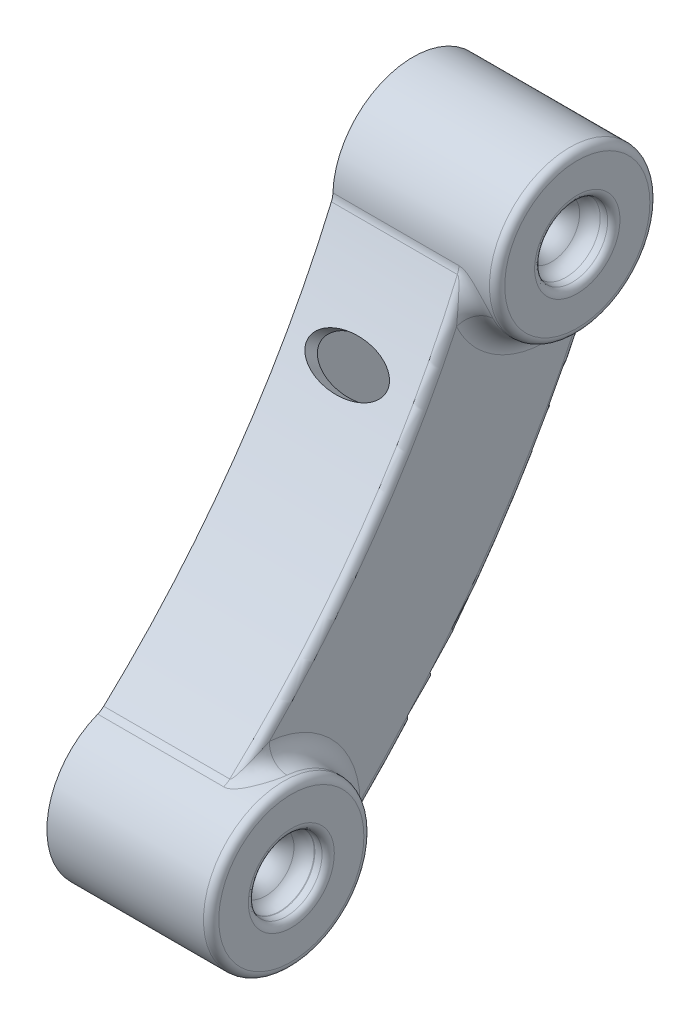
SolidWorks part; units mm, degrees
material "ABS"
ref_plane "Front Plane" through (0, 0, 0) normal (0, 0, 1) x (1, 0, 0)
ref_plane "Top Plane" through (0, 0, 0) normal (0, 1, 0) x (1, 0, 0)
ref_plane "Right Plane" through (0, 0, 0) normal (1, 0, 0) x (0, 0, -1)
sketch "Sketch1" plane through (0, 0, 0) normal (1, 0, 0) x (0, 0, -1)
  arc A0 (41.5746, 47.3049) -> (-33.3061, -58.963) centre (-210.024, 145.0757) cw construction
  arc A1 (-20.6251, -73.6045) -> (59.629, 40.289) centre (-210.024, 145.0757) ccw
  arc A2 (-45.9871, -44.3215) -> (23.5203, 54.3208) centre (-210.024, 145.0757) ccw
  arc A3 (-45.9871, -44.3215) -> (-20.6251, -73.6045) centre (-33.3061, -58.963) ccw
  arc A4 (59.629, 40.289) -> (23.5203, 54.3208) centre (41.5746, 47.3049) ccw
  point P3 (10.6273, -10.4043)
  dimension "D1" = 130
extrude "Boss-Extrude1" add sketch "Sketch1" along normal blind 40
fillet "Fillet1" radius 2 4 edges at (40, 0.7527, 5.2063) (40, 65.3593, -48.5905) (40, -21.5613, -26.4609) (40, -71.644, 47.9476)
fillet "Fillet2" radius 2 4 edges at (0, -21.5613, -26.4609) (0, 65.3593, -48.5905) (0, 0.7527, 5.2063) (0, -71.644, 47.9476)
sketch "Sketch3" plane through (40, 0, 0) normal (1, 0, 0) x (0, 0, -1)
  circle A0 centre (41.5746, 47.3049) radius 21
  circle A1 centre (-33.3061, -58.963) radius 21
  dimension "D1" = 42
  dimension "D2" = 42
extrude "Boss-Extrude2" add sketch "Sketch3" along normal blind 10 and the other way blind 40
fillet "Fillet3" radius 2 4 edges at (0, -73.0553, 48.8755) (0, 66.7079, -49.6074) (50, 47.3049, -62.5746) (50, -58.963, 12.3061)
sketch "Sketch4" plane through (50, 0, 0) normal (1, 0, 0) x (0, 0, -1)
  circle A0 centre (41.5746, 47.3049) radius 9
  circle A1 centre (-33.3061, -58.963) radius 9
  dimension "D1" = 18
  dimension "D2" = 18
extrude "Cut-Extrude1" cut sketch "Sketch4" against normal blind 10
draft "Draft1" type of draft neutral plane draft angle 1 faces to draft 1 face at (40, -58.963, 24.3061) neutral plane through (40, -58.963, 33.3061) neutral plane normal (1, 0, 0) parameters "D1"=1
fillet "Fillet5" radius 5 1 edges at (40, -58.963, 24.3061)
fillet "Fillet6" radius 5 1 edges at (50, -58.963, 24.1316)
fillet "Fillet7" radius 5 1 edges at (50, 47.3049, -50.5746)
fillet "Fillet8" radius 5 1 edges at (40, 47.3049, -50.5746)
sketch "Sketch5" plane through (0, 0, 0) normal (-1, 0, 0) x (0, 0, 1)
  arc A12 (-53.1045, 34.8124) -> (17.6628, -65.6179) centre (210.024, 145.0757) ccw
  arc A13 (17.6628, -65.6179) -> (38.1002, -42.653) centre (33.3061, -58.963) ccw
  arc A14 (-24.6025, 46.3323) -> (38.1002, -42.653) centre (210.024, 145.0757) ccw
  arc A15 (-24.6025, 46.3323) -> (-53.1045, 34.8124) centre (-41.5746, 47.3049) ccw
  arc A16 (-53.1045, 34.8124) -> (17.6628, -65.6179) centre (210.024, 145.0757) ccw
  arc A17 (17.6628, -65.6179) -> (38.1002, -42.653) centre (33.3061, -58.963) ccw
  arc A18 (-24.6025, 46.3323) -> (38.1002, -42.653) centre (210.024, 145.0757) ccw
  arc A19 (-24.6025, 46.3323) -> (-53.1045, 34.8124) centre (-41.5746, 47.3049) ccw
  point P3 (-10.8163, -10.5375)
  dimension "D1" = 2
extrude "Cut-Extrude2" cut sketch "Sketch5" against normal blind 35
sketch "Sketch6" plane through (0, 0, 0) normal (-1, 0, 0) x (0, 0, 1)
  arc A4 (-54.7852, 33.6491) -> (16.0019, -66.8092) centre (210.024, 145.0757) ccw
  arc A5 (16.0019, -66.8092) -> (39.1199, -40.8743) centre (33.3061, -58.963) ccw
  arc A6 (-22.5845, 46.6942) -> (39.1199, -40.8743) centre (210.024, 145.0757) ccw
  arc A7 (-22.5845, 46.6942) -> (-54.7852, 33.6491) centre (-41.5746, 47.3049) ccw
  arc A8 (-54.7852, 33.6491) -> (16.0019, -66.8092) centre (210.024, 145.0757) ccw
  arc A9 (16.0019, -66.8092) -> (39.1199, -40.8743) centre (33.3061, -58.963) ccw
  arc A10 (-22.5845, 46.6942) -> (39.1199, -40.8743) centre (210.024, 145.0757) ccw
  arc A11 (-22.5845, 46.6942) -> (-54.7852, 33.6491) centre (-41.5746, 47.3049) ccw
  dimension "D1" = 0
extrude "Boss-Extrude3" add sketch "Sketch6" against normal blind 7
sketch "Sketch7" plane through (0, 0, 0) normal (-1, 0, 0) x (0, 0, 1)
  circle A0 centre (-41.5746, 47.3049) radius 11
  circle A1 centre (33.3061, -58.963) radius 11
  dimension "D1" = 22
  dimension "D2" = 22
extrude "Cut-Extrude3" cut sketch "Sketch7" against normal blind 3
sketch "Sketch8" plane through (3, 0, 0) normal (-1, 0, 0) x (0, 0, 1)
  circle A0 centre (-41.5746, 47.3049) radius 1.5
  circle A1 centre (33.3061, -58.963) radius 1.5
  dimension "D1" = 3
  dimension "D2" = 3
extrude "Cut-Extrude4" cut sketch "Sketch8" against normal blind 13
sketch "Sketch9" plane through (0, 0, 0) normal (-1, 0, 0) x (0, 0, 1)
  arc A0 (5.2471, -45.5881) -> (19.5425, -31.0693) centre (28.8142, -54.4955) cw construction
  arc A1 (17.9088, -26.9417) -> (1.0947, -44.0186) centre (28.8142, -54.4955) ccw
  arc A2 (21.1761, -35.1969) -> (9.3995, -47.1575) centre (28.8142, -54.4955) ccw
  arc A3 (21.1761, -35.1969) -> (17.9088, -26.9417) centre (19.5425, -31.0693) ccw
  arc A4 (1.0947, -44.0186) -> (9.3995, -47.1575) centre (5.2471, -45.5881) ccw
  point P3 (10.8616, -36.8191)
extrude "Cut-Extrude5" cut sketch "Sketch9" against normal blind 13
sketch "Sketch10" plane through (0, 0, 0) normal (-1, 0, 0) x (0, 0, 1)
  line L1 (30.1932, -32.2559) -> (33.1416, -35.1969)
  line L2 (33.1416, -35.1969) -> (8.8115, -59.9933)
  line L3 (8.8115, -59.9933) -> (5.9216, -57.1173)
  line L5 (3.6776, -49.7405) -> (1.1214, -52.1539)
  line L6 (1.1214, -52.1539) -> (5.9216, -57.1173)
  line L7 (21.1761, -35.1969) -> (28.4389, -30.4591)
  line L8 (28.4389, -30.4591) -> (30.1932, -32.2559)
  arc A0 (1.0947, -44.0186) -> (9.3995, -47.1575) centre (5.2471, -45.5881) ccw construction
  arc A3 (21.1761, -35.1969) -> (9.3995, -47.1575) centre (28.8142, -54.4955) ccw construction
  arc A4 (3.6776, -49.7405) -> (9.3995, -47.1575) centre (5.2471, -45.5881) ccw
  arc A7 (21.1761, -35.1969) -> (9.3995, -47.1575) centre (28.8142, -54.4955) ccw
  arc A8 (-22.5845, 46.6942) -> (39.1199, -40.8743) centre (210.024, 145.0757) ccw construction
  arc A9 (-54.7852, 33.6491) -> (16.0019, -66.8092) centre (210.024, 145.0757) ccw construction
extrude "Boss-Extrude4" add sketch "Sketch10" against normal blind 36
sketch "Sketch11" plane through (35, 0, 0) normal (-1, 0, 0) x (0, 0, 1)
  circle A0 centre (33.3061, -58.963) radius 1.5
  circle A1 centre (-41.5746, 47.3049) radius 1.5
extrude "Cut-Extrude6" cut sketch "Sketch11" against normal through all
fillet "Fillet9" radius 5 14 edges at (0.768, -67.7575, 14.7049) (20, -68.0143, 14.3569) (38.5897, -67.8015, 14.2567) (40, -44.8707, 17.7367) (0.7707, -39.4834, 39.9383) (20, -39.1127, 40.1593) (0.7707, 46.9969, -20.9993) (20, 47.0803, -20.5758) (0.768, 32.7467, -56.1146) (20, 32.5055, -56.4735) (39.177, 31.8304, -55.7711) (40, 27.902, -33.5419) (39.2032, -38.8228, 39.2535) (38.6276, 46.832, -20.58)
sketch "Sketch12" plane through (0, 0, 0) normal (-1, 0, 0) x (0, 0, 1)
  circle A0 centre (-41.5746, 47.3049) radius 11
  circle A1 centre (-41.5746, 47.3049) radius 1.5
  circle A2 centre (33.3061, -58.963) radius 11
  circle A3 centre (33.3061, -58.963) radius 1.5
extrude "Boss-Extrude5" add sketch "Sketch12" against normal blind 40
sketch "Sketch14" plane through (0, 0, 0) normal (-1, 0, 0) x (0, 0, 1)
  arc A12 (30.5959, -28.374) -> (32.3293, -30.1495) centre (210.0229, 145.0746) ccw
  arc A13 (-19.5747, 47.2814) -> (30.5959, -28.374) centre (210.024, 145.0757) ccw
  arc A14 (-19.5747, 47.2814) -> (-57.3202, 31.9401) centre (-41.5746, 47.3049) ccw
  arc A15 (-57.3202, 31.9401) -> (13.5396, -68.6214) centre (210.024, 145.0757) ccw
  arc A16 (13.5396, -68.6214) -> (40.6855, -38.2375) centre (33.3061, -58.963) ccw
  arc A17 (32.3293, -30.1495) -> (40.6855, -38.2375) centre (210.024, 145.0757) ccw
  arc A18 (30.5959, -28.374) -> (32.3293, -30.1495) centre (210.0229, 145.0746) ccw
  arc A19 (-19.5747, 47.2814) -> (30.5959, -28.374) centre (210.024, 145.0757) ccw
  arc A20 (-19.5747, 47.2814) -> (-57.3202, 31.9401) centre (-41.5746, 47.3049) ccw
  arc A21 (-57.3202, 31.9401) -> (13.5396, -68.6214) centre (210.024, 145.0757) ccw
  arc A22 (13.5396, -68.6214) -> (40.6855, -38.2375) centre (33.3061, -58.963) ccw
  arc A23 (32.3293, -30.1495) -> (40.6855, -38.2375) centre (210.024, 145.0757) ccw
  dimension "D1" = 3
extrude "Cut-Extrude7" cut sketch "Sketch14" against normal blind 5
ref_plane "Plane1" through (0, 8.2155, 11.6591) normal (0, 0.576, 0.8174) x (1, 0, 0)
sketch "Sketch15" plane through (0, 8.2155, 11.6591) normal (0, 0.576, 0.8174) x (1, 0, 0)
  ellipse E0 centre (20.7051, 23.5238) end of major axis (31.398, 23.5238) minor radius 5.9262
extrude "Cut-Extrude8" cut sketch "Sketch15" against normal blind 27
sketch "Sketch16" plane through (5, 0, 0) normal (-1, 0, 0) x (0, 0, 1)
  circle A0 centre (33.3061, -58.963) radius 11
  circle A1 centre (33.3061, -58.963) radius 1.5
  circle A2 centre (-41.5746, 47.3049) radius 1.5
  circle A3 centre (-41.5746, 47.3049) radius 11
  dimension "D1" = 22
  dimension "D2" = 22
extrude "Cut-Extrude9" cut sketch "Sketch16" against normal blind 3
sketch "Sketch17" plane through (5, 0, 0) normal (-1, 0, 0) x (0, 0, 1)
  circle A0 centre (-41.5746, 47.3049) radius 11
  circle A1 centre (-41.5746, 47.3049) radius 19
  circle A2 centre (33.3061, -58.963) radius 11
  circle A3 centre (33.3061, -58.963) radius 19
  dimension "D1" = 38
  dimension "D2" = 38
extrude "Boss-Extrude6" add sketch "Sketch17" against normal blind 33
sketch "Sketch19" plane through (5, 0, 0) normal (-1, 0, 0) x (0, 0, 1)
  point P0 (33.3061, -58.963)
  point P1 (-41.5746, 47.3049)
sketch "Sketch20" plane through (40, 0, 0) normal (1, 0, 0) x (0, 0, -1)
  circle A0 centre (41.5746, 47.3049) radius 4
  circle A1 centre (-33.3061, -58.963) radius 4.0865
extrude "Cut-Extrude10" cut sketch "Sketch20" against normal blind 20
fillet "Fillet10" radius 10 1 edges at (40, 47.3049, -45.5746)
fillet "Fillet11" radius 10 1 edges at (40, -58.963, 29.2196)
sketch "Sketch21" plane through (50, 0, 0) normal (1, 0, 0) x (0, 0, -1)
  circle A0 centre (41.5746, 47.3049) radius 21
  circle A1 centre (-33.3061, -58.963) radius 21
extrude "Cut-Extrude11" cut sketch "Sketch21" against normal blind 2
fillet "Fillet12" radius 2 2 edges at (48, -58.963, 12.3061) (48, -58.963, 43.3942)
fillet "Fillet13" radius 2 2 edges at (48, 47.3049, -62.5746) (48, 47.3049, -31.5746)
sketch "Sketch22" plane through (8, 0, 0) normal (-1, 0, 0) x (0, 0, 1)
  circle A0 centre (-36.3312, 51.9424) radius 1.25
  circle A1 centre (-41.5746, 47.3049) radius 1.5 construction
  circle A2 centre (-36.9371, 42.0615) radius 1.25
  circle A3 centre (-46.8181, 42.6674) radius 1.25
  circle A4 centre (-46.2122, 52.5483) radius 1.25
  dimension "D1" = 2.5
  dimension "D2" = 7
  dimension "D3" = 4
extrude "Cut-Extrude12" cut sketch "Sketch22" against normal blind 4
sketch "Sketch23" plane through (8, 0, 0) normal (-1, 0, 0) x (0, 0, 1)
  circle A0 centre (39.244, -55.2561) radius 1.15
  circle A1 centre (37.0131, -64.9009) radius 1.15
  circle A2 centre (27.3682, -62.6699) radius 1.15
  circle A3 centre (29.5992, -53.0251) radius 1.15
  dimension "D1" = 2.3
  dimension "D2" = 7
  dimension "D3" = 4
extrude "Cut-Extrude13" cut sketch "Sketch23" against normal blind 4
